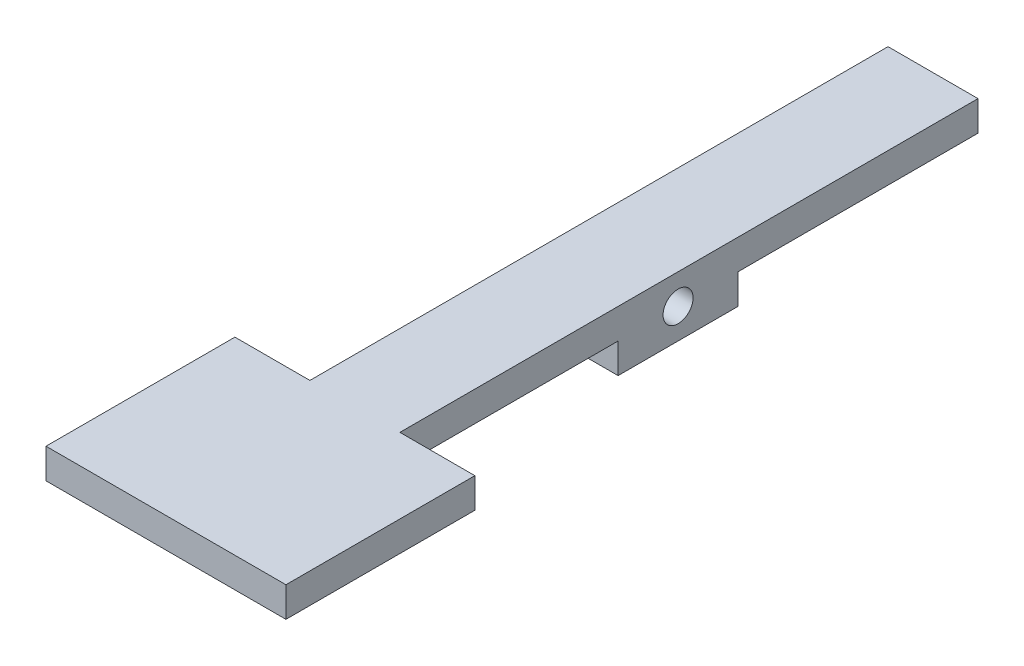
SolidWorks part; units mm, degrees
material "6061 Alloy"
ref_plane "Front Plane" through (0, 0, 0) normal (0, 0, 1) x (1, 0, 0)
ref_plane "Top Plane" through (0, 0, 0) normal (0, 1, 0) x (1, 0, 0)
ref_plane "Right Plane" through (0, 0, 0) normal (1, 0, 0) x (0, 0, -1)
sketch "Sketch1" plane through (0, 0, 0) normal (1, 0, 0) x (0, 0, -1)
  line L0 (0, 1.5875) -> (0, -1.5875)
  line L1 (0, -1.5875) -> (-25.4, -1.5875)
  line L5 (-76.2, 1.5875) -> (0, 1.5875)
  line L6 (-38.1, -1.5875) -> (-76.2, -1.5875)
  line L8 (-38.1, -1.5875) -> (-38.1, -4.7625)
  line L9 (-38.1, -4.7625) -> (-25.4, -4.7625)
  line L10 (-25.4, -1.5875) -> (-25.4, -4.7625)
  line L11 (-76.2, 1.5875) -> (-76.2, -1.5875)
  circle A0 centre (-31.75, -1.5875) radius 1.5875
  point P14 (-31.75, -4.7625)
  dimension "D6" = 3.175
  dimension "D1" = 3.175
  dimension "D4" = 76.2
  dimension "D5" = 3.175
  dimension "D7" = 12.7
  dimension "D8" = 38.1
extrude "Boss-Extrude1" add sketch "Sketch1" along normal blind 9.525 contours L5 | L10 L1 L0 L5 L6 L8 L9 A0 region at (0, -0.4208, 37.3499)
ref_plane "Center Plane" through (4.7625, 0, 0) normal (1, 0, 0) x (0, 0, -1)
sketch "Sketch3" plane through (4.7625, 0, 0) normal (1, 0, 0) x (0, 0, -1)
  line L2 (-76.2, -1.5875) -> (-61.2, -1.5875)
  line L4 (-61.2, -1.5875) -> (-61.2, 1.5875)
  line L5 (-76.2, 1.5875) -> (0, 1.5875) construction
  line L6 (-61.2, 1.5875) -> (-76.2, 1.5875)
  line L7 (-76.2, 1.5875) -> (-76.2, -1.5875)
  line L9 (-76.2, 1.5875) -> (-81.2, 1.5875)
  line L10 (-76.2, 1.5875) -> (-76.2, -1.5875)
  line L11 (-76.2, -1.5875) -> (-81.2, -1.5875)
  line L12 (-81.2, 1.5875) -> (-81.2, -1.5875)
  line L13 (-76.2, 1.5875) -> (-76.2, -1.5875) construction
  line L14 (-38.1, -1.5875) -> (-76.2, -1.5875) construction
  dimension "D1" = 15
  dimension "D2" = 20
extrude "Boss-Extrude2" add sketch "Sketch3" along normal mid plane 25.4 contours L6 L7 L2 L4 | L9 L12 L11 L7 region at (4.7625, 0, 68.7) region at (4.7625, 0, 78.7)
fillet "Fillet1" [suppressed] radius 6.35
sketch "Sketch4" plane through (9.525, 0, 0) normal (1, 0, 0) x (0, 0, -1)
  line L0 (-38.1, -4.7625) -> (-25.4, -4.7625) construction
  line L1 (-25.4, -1.5875) -> (0, -1.5875)
  line L2 (-25.4, -1.5875) -> (-25.4, -4.7625)
  line L3 (-25.4, -4.7625) -> (0, -4.7625)
  line L4 (0, -1.5875) -> (0, -4.7625)
extrude "Boss-Extrude3" [suppressed] add sketch "Sketch4" against normal up to surface (9.525 mm away) up to face at (0, -1.5875, 30.1625)
